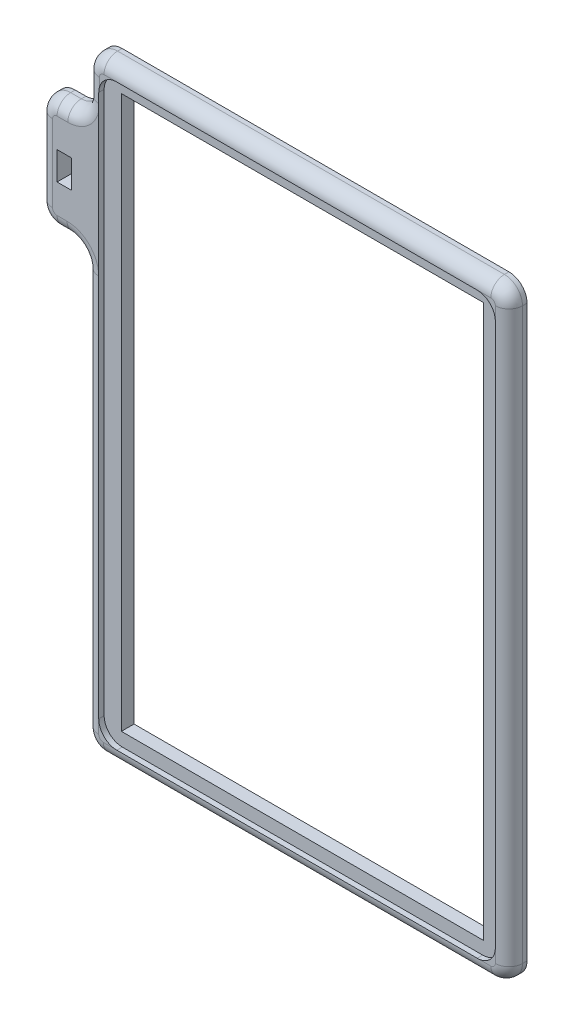
SolidWorks part; units mm, degrees
ref_plane "Piano frontale" through (0, 0, 0) normal (0, 0, 1) x (1, 0, 0)
ref_plane "Piano superiore" through (0, 0, 0) normal (0, 1, 0) x (1, 0, 0)
ref_plane "Piano destro" through (0, 0, 0) normal (1, 0, 0) x (0, 0, -1)
sketch "Schizzo1" plane through (0, 0, 0) normal (0, 0, 1) x (1, 0, 0)
  line L5 (-42.8, -66.9) -> (42.8, -66.9)
  line L6 (46.8, 62.9) -> (46.8, -62.9)
  line L7 (-42.6381, 66.9) -> (42.8, 66.9)
  line L8 (-46.6381, 62.9) -> (-46.6381, 57.7765)
  line L13 (-50.6381, 53.7765) -> (-53, 53.7765)
  line L14 (-53, 44.3765) -> (-49.8, 44.3765)
  line L15 (-53, 44.3765) -> (-53, 38.1765)
  line L16 (-53, 38.1765) -> (-49.8, 38.1765)
  line L17 (-49.8, 44.3765) -> (-49.8, 38.1765)
  line L19 (-57, 49.7765) -> (-57, 32.7765)
  line L20 (-53, 28.7765) -> (-50.8, 28.7765)
  line L21 (-46.8, 24.7765) -> (-46.8, -62.9)
  line L22 (-63.8715, 41.2765) -> (-33.9171, 41.2765) construction
  line L30 (40.8, -60.9) -> (40.8, -60.8965)
  line L39 (-40, 61) -> (40, 61)
  line L40 (-40, 61) -> (-40, -61)
  line L41 (-40, -61) -> (40, -61)
  line L42 (40, 61) -> (40, -61)
  arc A14 (-50.8, 28.7765) -> (-46.8, 24.7765) centre (-50.8, 24.7765) cw
  arc A15 (-57, 32.7765) -> (-53, 28.7765) centre (-53, 32.7765) ccw
  arc A16 (-53, 53.7765) -> (-57, 49.7765) centre (-53, 49.7765) ccw
  arc A17 (-46.6381, 57.7765) -> (-50.6381, 53.7765) centre (-50.6381, 57.7765) cw
  arc A18 (-46.8, -62.9) -> (-42.8, -66.9) centre (-42.8, -62.9) ccw
  arc A19 (42.8, -66.9) -> (46.8, -62.9) centre (42.8, -62.9) ccw
  arc A20 (46.8, 62.9) -> (42.8, 66.9) centre (42.8, 62.9) ccw
  arc A21 (-46.6381, 62.9) -> (-42.6381, 66.9) centre (-42.6381, 62.9) cw
  point P15 (-43.8, 63.9)
  point P38 (-57, 28.7765)
  point P41 (-57, 53.7765)
  dimension "D14" = 4
  dimension "D3" = 4
  dimension "D6" = 4
  dimension "D7" = 6.2
  dimension "D8" = 3.2
  dimension "D9" = 25
  dimension "D10" = 3.1
  dimension "D11" = 12.5
  dimension "D12" = 3
  dimension "D13" = 4
  dimension "D5" = 66.9
  dimension "D18" = 93.6
  dimension "D4" = 46.8
  dimension "D2" = 133.8
  dimension "D15" = 80
  dimension "D16" = 40
  dimension "D17" = 122
  dimension "D19" = 61
extrude "Estrusione-Estrusione1" add sketch "Schizzo1" along normal blind 4
sketch "Schizzo5" plane through (0, 0, 4) normal (0, 0, 1) x (1, 0, 0)
  line L0 (-39.8, 63.9) -> (39.8, 63.9)
  line L1 (-43.8, 59.9) -> (-43.8, -59.9)
  line L2 (-39.8, -63.9) -> (39.8, -63.9)
  line L3 (43.8, 59.9) -> (43.8, -59.9)
  arc A0 (-43.8, -59.9) -> (-39.8, -63.9) centre (-39.8, -59.9) ccw
  arc A1 (39.8, -63.9) -> (43.8, -59.9) centre (39.8, -59.9) ccw
  arc A2 (39.8, 63.9) -> (43.8, 59.9) centre (39.8, 59.9) cw
  arc A3 (-39.8, 63.9) -> (-43.8, 59.9) centre (-39.8, 59.9) ccw
  line M29 (40, -61) -> (-40, -61)
  line M30 (-40, -61) -> (-40, 61)
  line M31 (-40, 61) -> (40, 61)
  line M32 (40, 61) -> (40, -61)
  dimension "D1" = 4
  dimension "D2" = 127.8
  dimension "D3" = 87.6
  dimension "D4" = 43.8
  dimension "D5" = 63.9
extrude "Taglio-Estrusione4" cut sketch "Schizzo5" against normal blind 1.2 contours L0 A3 L1 A0 L2 A1 L3 A2 M32 M29 M30 M31 region at (0, 62.3506, 4)
sketch "Schizzo6" plane through (0, 0, 0) normal (0, 0, -1) x (-1, 0, 0)
  line L0 (51.3449, 52.3188) -> (51.3449, 25.788) construction
  line L1 (54.8845, 41.2765) -> (38.8101, 41.2765) construction
  line L2 (53, 44.3765) -> (49.8, 44.3765) construction
  circle A0 centre (51.3449, 48.7765) radius 0.75
  circle A1 centre (51.3449, 33.7765) radius 0.75
  dimension "D1" = 1.5
  dimension "D2" = 1.5
  dimension "D3" = 15
  dimension "D4" = 7.5
  dimension "D5" = 3.1
extrude "Taglio-Estrusione5" cut sketch "Schizzo6" against normal blind 3
fillet "Raccordo1" radius 3 16 edges at (-45.4665, 65.7284, 4) (-46.6381, 60.3382, 4) (-47.8097, 54.948, 4) (-51.8191, 53.7765, 4) (-55.8284, 52.6049, 4) (-57, 41.2765, 4) (-55.8284, 29.948, 4) (-51.9, 28.7765, 4) (-47.9716, 27.6049, 4) (-46.8, -19.0618, 4) (-45.6284, -65.7284, 4) (0, -66.9, 4) (45.6284, -65.7284, 4) (46.8, 0, 4) (45.6284, 65.7284, 4) (0.0809, 66.9, 4)
equation "\"D4@Schizzo1\"=\"D18@Schizzo1\"/2"
equation "\"D5@Schizzo1\"=\"D2@Schizzo1\"/2"
equation "\"D19@Schizzo1\"=\"D17@Schizzo1\"/2"
equation "\"D4@Schizzo5\"=\"D3@Schizzo5\"/2"
equation "\"D5@Schizzo5\"=\"D2@Schizzo5\"/2"
equation "\"D16@Schizzo1\"=\"D15@Schizzo1\"/2"
